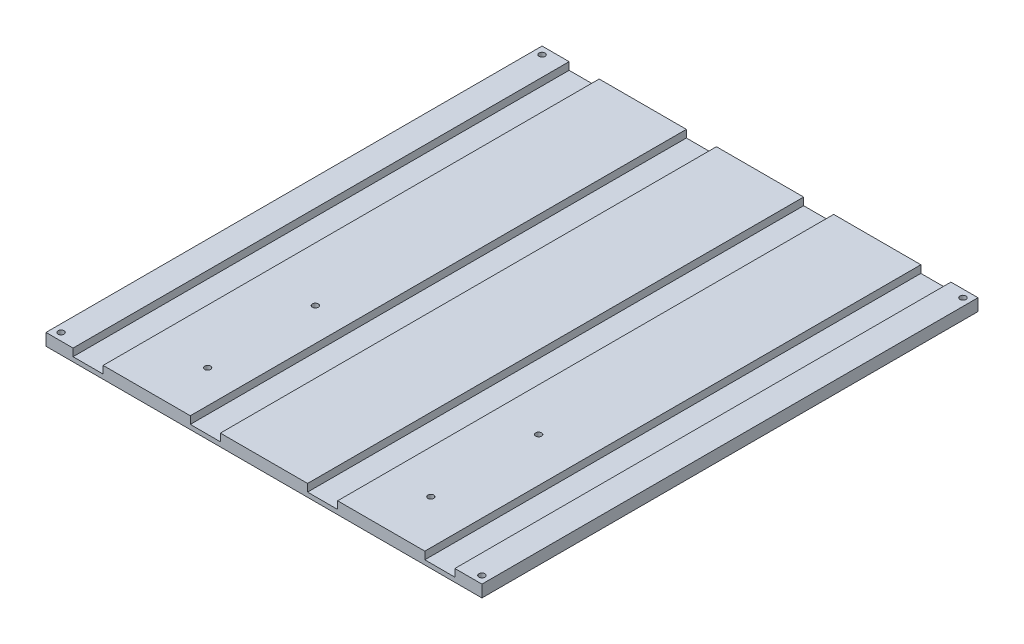
SolidWorks part; units mm, degrees
ref_plane "Front Plane" through (0, 0, 0) normal (0, 0, 1) x (1, 0, 0)
ref_plane "Top Plane" through (0, 0, 0) normal (0, 1, 0) x (1, 0, 0)
ref_plane "Right Plane" through (0, 0, 0) normal (1, 0, 0) x (0, 0, -1)
sketch "Sketch2" plane through (0, 0, 0) normal (0, 1, 0) x (1, 0, 0)
  line L0 (-24.5, -82.5) -> (-24.5, 82.5)
  line L1 (-72.5, -82.5) -> (72.5, -82.5)
  line L2 (-72.5, -82.5) -> (-72.5, 82.5)
  line L3 (-72.5, 82.5) -> (72.5, 82.5)
  line L4 (72.5, -82.5) -> (72.5, 82.5)
  line L5 (-63.5, -82.5) -> (-53.5, -82.5)
  line L6 (-63.5, -82.5) -> (-63.5, 82.5)
  line L7 (-63.5, 82.5) -> (-53.5, 82.5)
  line L8 (-53.5, -82.5) -> (-53.5, 82.5)
  line L9 (-63.5, -82.5) -> (-53.5, 82.5) construction
  line L10 (-63.5, 82.5) -> (-53.5, -82.5) construction
  line L11 (-24.5, -82.5) -> (-14.5, -82.5)
  line L12 (-14.5, -82.5) -> (-14.5, 82.5)
  line L13 (-24.5, 82.5) -> (-14.5, 82.5)
  line L14 (14.5, -82.5) -> (14.5, 82.5)
  line L15 (14.5, -82.5) -> (24.5, -82.5)
  line L16 (24.5, -82.5) -> (24.5, 82.5)
  line L17 (14.5, 82.5) -> (24.5, 82.5)
  line L18 (53.5, -82.5) -> (53.5, 82.5)
  line L19 (53.5, -82.5) -> (63.5, -82.5)
  line L20 (63.5, -82.5) -> (63.5, 82.5)
  line L21 (53.5, 82.5) -> (63.5, 82.5)
  point P0 (0, 0)
  point P6 (0, 82.5)
  point P7 (-72.5, 0)
  point P8 (-58.5, 0)
  dimension "D1" = 145
  dimension "D2" = 165
  dimension "D3" = 10
  dimension "D4" = 165
  dimension "D5" = 58.5
  dimension "D6" = 4
  dimension "D7" = 29
extrude "Boss-Extrude1" add sketch "Sketch2" against normal blind 4 contours L2 L1 L4 L3
extrude "Cut-Extrude1" cut sketch "Sketch2<3>" against normal blind 2.5 contours L6 L5 L8 L7 | L0 L13 L12 L11 | L14 L17 L16 L15 | L18 L21 L20 L19
sketch "Sketch2<3>" plane through (0, 0, 0) normal (0, 1, 0) x (1, 0, 0) same geometry as "Sketch2"
sketch "Sketch3" plane through (0, -4, 0) normal (0, -1, 0) x (1, 0, 0)
  line L0 (-70, -80) -> (70, 80)
  line L1 (-70, 80) -> (70, 80) construction
  line L2 (-70, 80) -> (-70, -80) construction
  line L3 (-70, -80) -> (70, -80) construction
  line L4 (70, 80) -> (70, -80) construction
  circle A0 centre (-70, 80) radius 1
  circle A1 centre (-70, 80) radius 1.25
  circle A2 centre (70, 80) radius 1.25
  circle A3 centre (70, 80) radius 1
  circle A4 centre (70, -80) radius 1.25
  circle A5 centre (70, -80) radius 1
  circle A6 centre (-70, -80) radius 1.25
  circle A7 centre (-70, -80) radius 1
  point P11 (0, 0)
  dimension "D1" = 2
  dimension "D2" = 2.5
  dimension "D5" = 2.5
  dimension "D6" = 2
  dimension "D7" = 2
  dimension "D8" = 2.5
  dimension "D9" = 2.5
  dimension "D10" = 2
  dimension "D3" = 160
  dimension "D4" = 140
extrude "Cut-Extrude3" cut sketch "Sketch3" against normal blind 5 contours A5 | A7 | A0 | A3
sketch "Sketch5" plane through (0, -4, 0) normal (0, 1, 0) x (1, 0, 0)
  line L1 (-35.4387, -29.9718) -> (38.8313, -29.9718) construction
  line L2 (-35.4387, -29.9718) -> (-35.4387, -65.8118) construction
  line L3 (-35.4387, -65.8118) -> (38.8313, -65.8118) construction
  line L4 (38.8313, -29.9718) -> (38.8313, -65.8118) construction
  circle A0 centre (-35.4387, -29.9718) radius 0.98
  circle A1 centre (38.8313, -29.9718) radius 0.98
  circle A2 centre (38.8313, -65.8118) radius 0.98
  circle A3 centre (-35.4387, -65.8118) radius 0.98
  dimension "D3" = 1.96
  dimension "D1" = 74.27
  dimension "D2" = 35.84
extrude "Cut-Extrude4" cut sketch "Sketch5" along normal blind 4 contours A0 | A1 | A2 | A3
